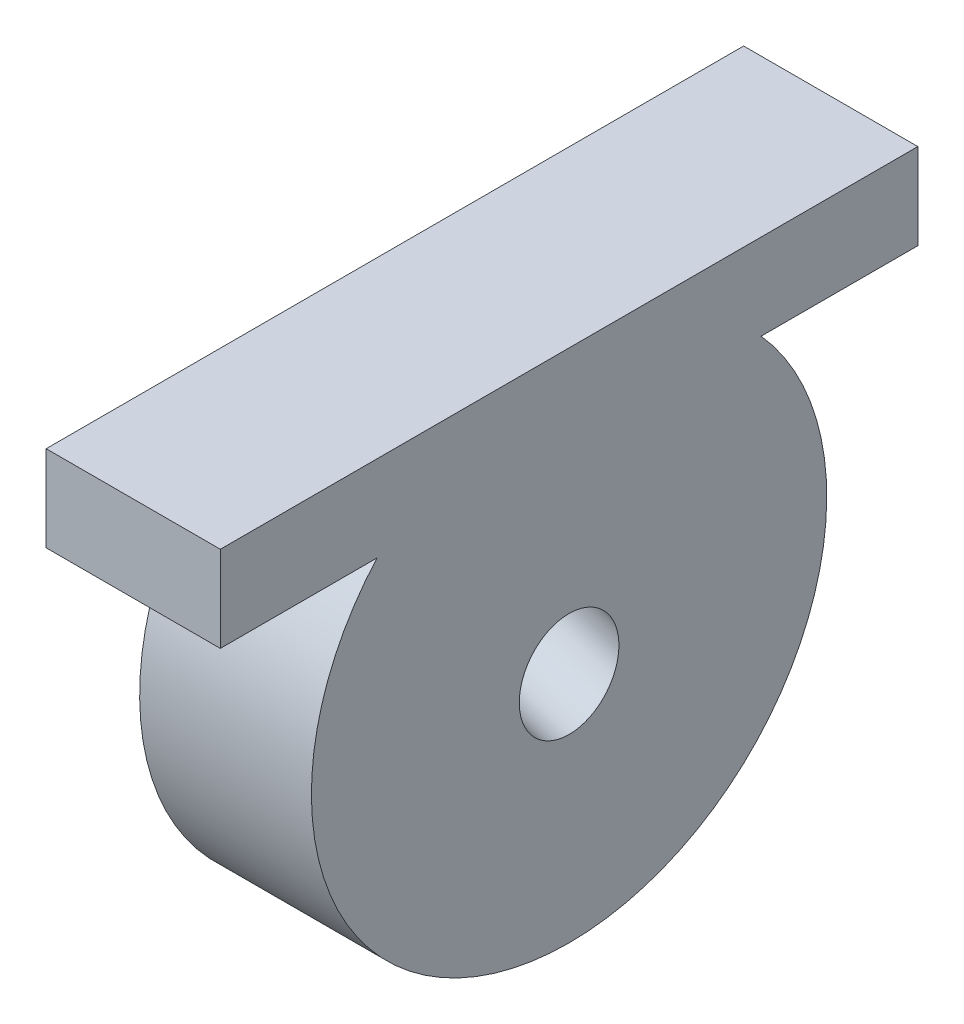
SolidWorks part; units mm, degrees
ref_plane "Front Plane" through (0, 0, 0) normal (0, 0, 1) x (1, 0, 0)
ref_plane "Top Plane" through (0, 0, 0) normal (0, 1, 0) x (1, 0, 0)
ref_plane "Right Plane" through (0, 0, 0) normal (1, 0, 0) x (0, 0, -1)
sketch "Sketch3" plane through (0, 717.6366, 0) normal (0, -1, 0) x (-1, 0, 0)
  line L0 (-524.1514, -762.9166) -> (-524.1514, -558.1792) construction
  line L1 (-524.1514, -712.1166) -> (-498.3984, -712.1166)
  line L2 (-524.1514, -712.1166) -> (-524.1514, -608.9792)
  line L3 (-524.1514, -608.9792) -> (-498.3984, -608.9792)
  line L4 (-498.3984, -712.1166) -> (-498.3984, -608.9792)
  line L5 (-498.3984, -762.9166) -> (-498.3984, -558.1792) construction
  line L6 (-524.1514, -762.9166) -> (-498.3984, -762.9166) construction
  line L7 (-524.1514, -558.1792) -> (-498.3984, -558.1792) construction
  dimension "D1" = 50.8
  dimension "D2" = 50.8
extrude "Boss-Extrude1" add sketch "Sketch3" along normal blind 12.7
sketch "Sketch4" plane through (524.1514, 0, 0) normal (1, 0, 0) x (0, 0, -1)
  line L0 (-660.5479, 717.6366) -> (-660.5479, 679.5366) construction
  line L1 (-608.9792, 717.6366) -> (-712.1166, 717.6366) construction
  circle A0 centre (-660.5479, 679.5366) radius 38.1
  dimension "D1" = 38.1
extrude "Boss-Extrude2" add sketch "Sketch4" against normal blind 25.4
ref_plane "Plane1" through (0, 0, 660.5479) normal (0, 0, 1) x (1, 0, 0)
sketch "Sketch5" plane through (0, 0, 660.5479) normal (0, 0, 1) x (1, 0, 0)
  line L0 (472.4505, 692.7093) -> (547.7665, 668.1914)
sweep "Cut-Sweep1" cut path "Sketch5" circular profile diameter 14.732 parameters "D3"=14.732
